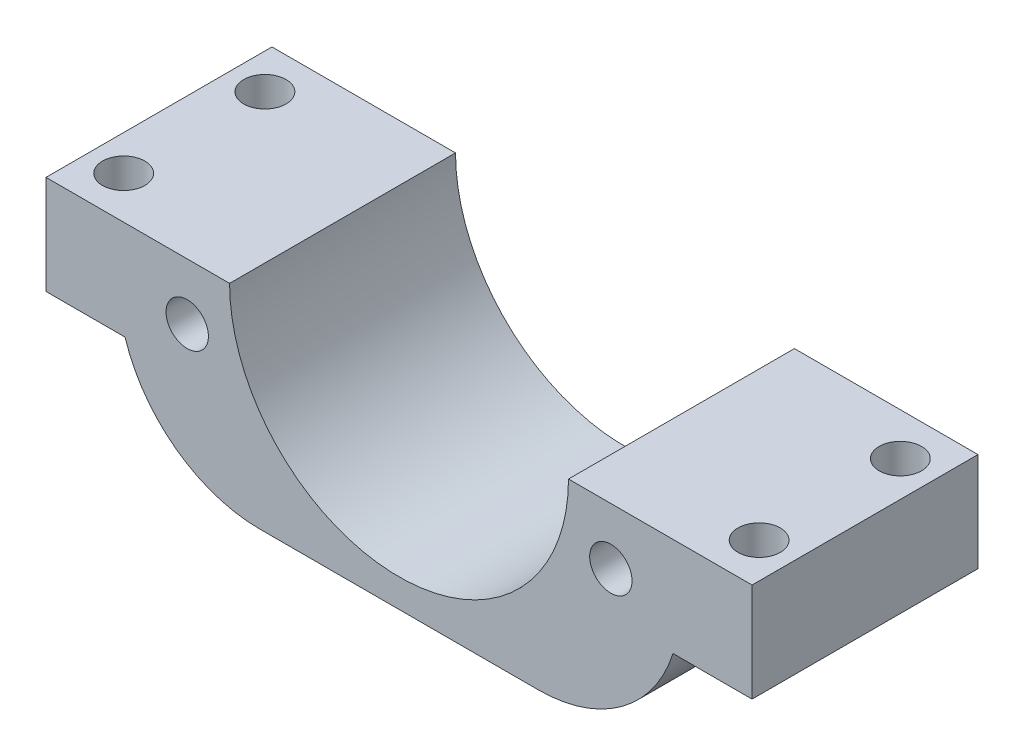
SolidWorks part; units mm, degrees
ref_plane "Front Plane" through (0, 0, 0) normal (0, 0, 1) x (1, 0, 0)
ref_plane "Top Plane" through (0, 0, 0) normal (0, 1, 0) x (1, 0, 0)
ref_plane "Right Plane" through (0, 0, 0) normal (1, 0, 0) x (0, 0, -1)
sketch "Sketch7" plane through (0, 0, 0) normal (0, 0, 1) x (1, 0, 0)
  line L17 (3.5981, 0.9) -> (42.4, 0.9)
  line L20 (-2, 14.9) -> (11, 14.9)
  line L21 (35, 14.9) -> (48, 14.9)
  line L24 (3.5981, 7.9) -> (-2, 7.9)
  line L25 (3.5981, 7.9) -> (3.5981, 0.9)
  line L26 (42.4, 7.9) -> (42.4, 0.9)
  line L29 (48, 7.9) -> (42.4, 7.9)
  line L31 (48, 14.9) -> (48, 7.9)
  line L32 (-2, 14.9) -> (-2, 7.9)
  circle A1 centre (8, 10.9) radius 1.5
  circle A2 centre (38, 10.9) radius 1.5
  arc A3 (11, 14.9) -> (35, 14.9) centre (23, 14.9) ccw
  dimension "D3" = 5.5981
  dimension "D4" = 13
  dimension "D10" = 7
  dimension "D11" = 3
  dimension "D12" = 5.6
  dimension "D13" = 7
  dimension "D15" = 3
  dimension "D7" = 13
  dimension "D8" = 4
  dimension "D2" = 24
  dimension "D16" = 10
  dimension "D5" = 13
  dimension "D6" = 10
  dimension "D9" = 4
  dimension "D14" = 7
extrude "Boss-Extrude11" add sketch "Sketch7" along normal blind 16 contours A3 L20 L32 L24 L25 L17 L26 L29 L31 L21 A2 A1 region at (4.1173, 4.4, 0)
ref_plane "Plane2" through (0, 7.9, 0) normal (0, -1, 0) x (-1, 0, 0)
sketch "Sketch8" plane through (0, 7.9, 0) normal (0, -1, 0) x (1, 0, 0)
  line L8 (-2, 0) -> (11, 0) construction
  line L9 (-2, 16) -> (-2, 0) construction
  line L11 (-2, 16) -> (11, 16) construction
  line L12 (48, 16) -> (48, 0) construction
  line L13 (35, 0) -> (48, 0) construction
  line L14 (35, 16) -> (48, 16) construction
  circle A0 centre (0.5, 13) radius 1.5
  circle A1 centre (45.5, 13) radius 1.5
  circle A2 centre (45.5, 3) radius 1.5
  circle A3 centre (0.5, 3) radius 1.5
  dimension "D1" = 3
  dimension "D2" = 3
  dimension "D3" = 2.5
  dimension "D4" = 2.5
  dimension "D5" = 3
  dimension "D6" = 2.5
  dimension "D7" = 3
  dimension "D8" = 3
  dimension "D9" = 2.5
extrude "Cut-Extrude1" cut sketch "Sketch8" against normal through all
fillet "Fillet1" radius 10 2 edges at (3.5981, 0.9, 8) (42.4, 0.9, 8)
